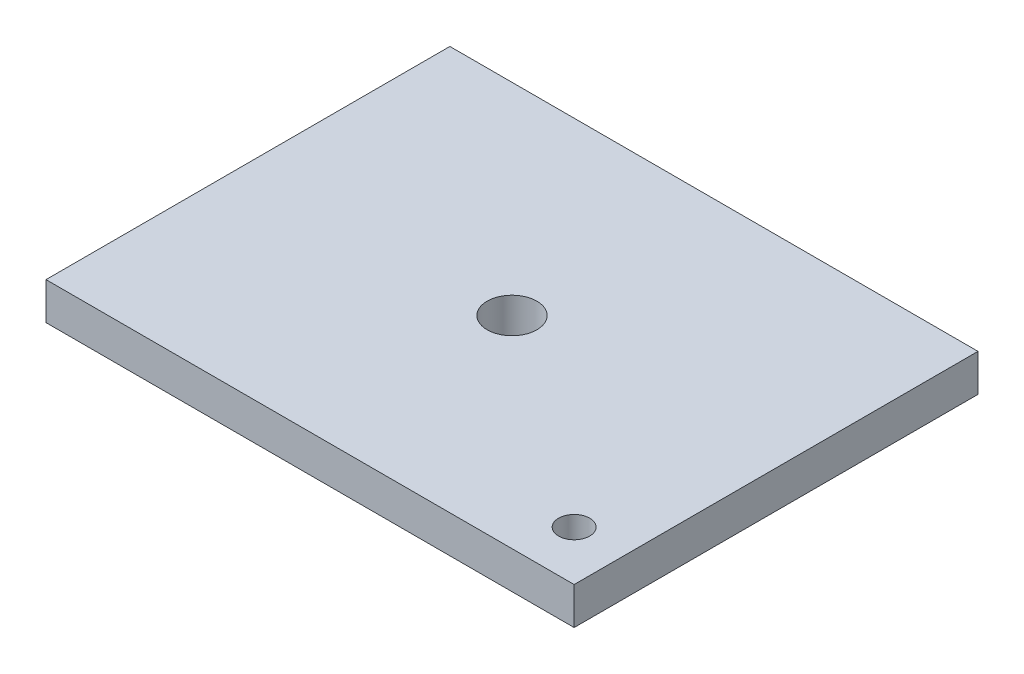
SolidWorks part; units mm, degrees
ref_plane "Спереди" through (0, 0, 0) normal (0, 0, 1) x (1, 0, 0)
ref_plane "Сверху" through (0, 0, 0) normal (0, 1, 0) x (1, 0, 0)
ref_plane "Справа" through (0, 0, 0) normal (1, 0, 0) x (0, 0, -1)
sketch "Эскиз1" plane through (0, 0, 0) normal (0, 1, 0) x (1, 0, 0)
  line L1 (0, 0) -> (85, 0)
  line L2 (0, 0) -> (0, -65)
  line L3 (0, -65) -> (85, -65)
  line L4 (85, 0) -> (85, -65)
  circle A0 centre (42.5, -32.5) radius 4
  dimension "D1" = 32.5
extrude "Вытянуть1" add sketch "Эскиз1" along normal blind 6
sketch "Эскиз2" plane through (0, 6, 0) normal (0, 1, 0) x (1, 0, 0)
  line L0 (85, -65) -> (85, 0) construction
  line L1 (0, -65) -> (85, -65) construction
  circle A0 centre (77, -57) radius 2.5
  point P6 (139.0864, 8.9031)
  dimension "D1" = 8
  dimension "D2" = 8
extrude "Вырез-Вытянуть1" cut sketch "Эскиз2" against normal through all
